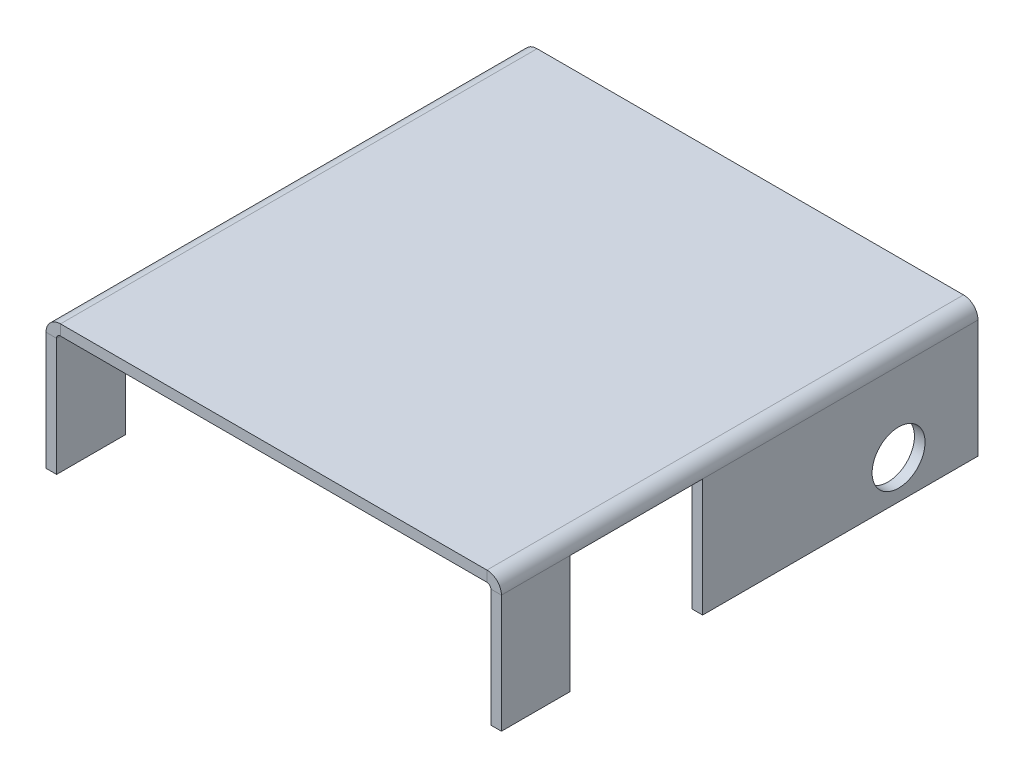
SolidWorks part; units mm, degrees
note: The reader was unsure of these and kept them because the rebuilt part matched: flange length of "Edge-Flange1", "Edge-Flange2".
ref_plane "Front Plane" through (0, 0, 0) normal (0, 0, 1) x (1, 0, 0)
ref_plane "Top Plane" through (0, 0, 0) normal (0, 1, 0) x (1, 0, 0)
ref_plane "Right Plane" through (0, 0, 0) normal (1, 0, 0) x (0, 0, -1)
sketch "Sketch1" plane through (0, 0, 0) normal (0, 1, 0) x (1, 0, 0)
  line L1 (4.0169, 90.0175) -> (90.0169, 90.0175)
  line L2 (4.0169, 90.0175) -> (4.0169, 0.0175)
  line L3 (4.0169, 0.0175) -> (90.0169, 0.0175)
  line L4 (90.0169, 90.0175) -> (90.0169, 0.0175)
  dimension "D1" = 86
  dimension "D2" = 90
base flange "Base-Flange1" sketch "Sketch1" thickness 2 reverse thickness direction no parameters "D1"=0.7366
edge flange "Edge-Flange1" sketch "Sketch8" flange angle 90 flange length 25 flange position material inside bend radius 0.7366 thickness 2 relief rectangular parameters "D6"=10
sketch "Sketch8" plane through (90.0169, -2, 0) normal (1, 0, 0) x (0, 0, 1)
  line L2 (-90.0175, 0) -> (-90.0175, 23)
  line L3 (-90.0175, 23) -> (-0.0175, 23)
  line L4 (-0.0175, 23) -> (-0.0175, 0)
  line L5 (-0.0175, 0) -> (-90.0175, 0) construction
  line L6 (-0.0175, 0) -> (-90.0175, 0)
bend "EdgeBend1" bend radius 0.7366 bend angle 90 parameters "D5"=1
edge flange "Edge-Flange2" sketch "Sketch11" flange angle 90 flange length 25 flange position material inside bend radius 0.7366 thickness 2 relief rectangular parameters "D6"=10
sketch "Sketch11" plane through (4.0169, -2, 0) normal (-1, 0, 0) x (0, 0, -1)
  line L0 (90.0175, 0) -> (0.0175, 0) construction
  line L1 (90.0175, 0) -> (0.0175, 0)
  line L2 (0.0175, 0) -> (0.0175, 23)
  line L3 (0.0175, 23) -> (90.0175, 23)
  line L4 (90.0175, 23) -> (90.0175, 0)
bend "EdgeBend2" bend radius 0.7366 bend angle 90 parameters "D5"=2
sketch "Sketch13" plane through (90.0169, 0, 0) normal (1, 0, 0) x (0, 0, -1)
  line L0 (0.0175, -25) -> (90.0175, -25) construction
  line L1 (38.0175, -25) -> (13.0175, -25)
  line L2 (38.0175, -25) -> (38.0175, -2.7366)
  line L3 (38.0175, -2.7366) -> (13.0175, -2.7366)
  line L4 (13.0175, -25) -> (13.0175, -2.7366)
  line L5 (0.0175, -2.7366) -> (90.0175, -2.7366) construction
  dimension "D1" = 25
  dimension "D2" = 13
extrude "Cut-Extrude1" cut sketch "Sketch13" against normal through all normal cut yes
sketch "Sketch15" plane through (4.0169, 0, 0) normal (-1, 0, 0) x (0, 0, 1)
  line L0 (-90.0175, -2.7366) -> (-38.0175, -2.7366) construction
  line L1 (-90.0175, -2.7366) -> (-90.0175, -25) construction
  circle A0 centre (-75.0175, -17.7366) radius 5
  dimension "D1" = 15
  dimension "D2" = 15
extrude "Cut-Extrude2" cut sketch "Sketch15" against normal through all normal cut yes
sketch "Bend-Lines1" [suppressed] plane through (0, 0, 0) normal (0, 1, 0) x (1, 0, 0)
sketch "Bounding-Box1" [suppressed] plane through (0, 0, 0) normal (0, 1, 0) x (1, 0, 0)
sheet metal parameters "Sheet-Metal1" thickness 2 parameters "D1"=0.7366
flat pattern "Flat-Pattern1" [suppressed]
sketch "Bend-Lines2" plane through (0, 0, 0) normal (0, 1, 0) x (1, 0, 0)
sketch3d "Bounding-Box2" [suppressed]
  line L0 (-90.0169, 0.0175, 0) -> (-0.0169, 0.0175, 0) construction
  line L1 (-90.0169, 90.0175, 0) -> (-0.0169, 90.0175, 0) construction
  line L2 (-90.0169, 0.0175, 0) -> (-90.0169, 90.0175, 0) construction
  line L3 (-0.0169, 0.0175, 0) -> (-0.0169, 90.0175, 0) construction
sheet metal parameters "Sheet-Metal2" thickness 2 parameters "D1"=0.7366
flat pattern "Flat-Pattern1"
sketch "Bend-Lines2" plane through (0, 0, 0) normal (0, 1, 0) x (1, 0, 0)
  line L0 (88.6442, 0.0175) -> (88.6442, 90.0175) construction
  line L1 (88.6442, 0.0175) -> (88.6442, 90.0175) construction
sketch3d "Bounding-Box2" [suppressed]
  line L0 (112.2715, 0.0175, 0) -> (0.0169, 0.0175, 0) construction
  line L1 (112.2715, 90.0175, 0) -> (0.0169, 90.0175, 0) construction
  line L2 (112.2715, 0.0175, 0) -> (112.2715, 90.0175, 0) construction
  line L3 (0.0169, 0.0175, 0) -> (0.0169, 90.0175, 0) construction
bend of the flat pattern "Flatten-<EdgeBend1>1"
sheet metal parameters "Sheet-Metal3" thickness 2 parameters "D1"=0.7366
flat pattern "Flat-Pattern1"
sketch "Bend-Lines2" plane through (0, 0, 0) normal (0, 1, 0) x (1, 0, 0)
  line L0 (88.6442, 0.0175) -> (88.6442, 90.0175) construction
  line L1 (88.6442, 0.0175) -> (88.6442, 90.0175) construction
  line L2 (1.3896, 90.0175) -> (1.3896, 0.0175) construction
  line L3 (1.3896, 90.0175) -> (1.3896, 0.0175) construction
sketch3d "Bounding-Box2" [suppressed]
  line L0 (112.2715, 0.0175, 0) -> (-22.2378, 0.0175, 0) construction
  line L1 (112.2715, 90.0175, 0) -> (-22.2378, 90.0175, 0) construction
  line L2 (112.2715, 0.0175, 0) -> (112.2715, 90.0175, 0) construction
  line L3 (-22.2378, 0.0175, 0) -> (-22.2378, 90.0175, 0) construction
bend of the flat pattern "Flatten-<EdgeBend1>1"
bend of the flat pattern "Flatten-<EdgeBend2>1"
sheet metal parameters "Sheet-Metal4" thickness 2 parameters "D1"=0.7366
flat pattern "Flat-Pattern1"
sketch "Bend-Lines2" plane through (0, 0, 0) normal (0, 1, 0) x (1, 0, 0)
  line L0 (88.6442, 0.0175) -> (88.6442, 90.0175) construction
  line L1 (88.6442, 0.0175) -> (88.6442, 90.0175) construction
  line L2 (1.3896, 90.0175) -> (1.3896, 0.0175) construction
  line L3 (1.3896, 90.0175) -> (1.3896, 0.0175) construction
sketch3d "Bounding-Box2" [suppressed]
  line L0 (112.2715, 0.0175, 0) -> (-22.2378, 0.0175, 0) construction
  line L1 (112.2715, 90.0175, 0) -> (-22.2378, 90.0175, 0) construction
  line L2 (112.2715, 0.0175, 0) -> (112.2715, 90.0175, 0) construction
  line L3 (-22.2378, 0.0175, 0) -> (-22.2378, 90.0175, 0) construction
bend of the flat pattern "Flatten-<EdgeBend1>1"
bend of the flat pattern "Flatten-<EdgeBend2>1"
sheet metal parameters "Sheet-Metal5" thickness 2 parameters "D1"=0.7366
flat pattern "Flat-Pattern1"
sketch "Bend-Lines2" plane through (0, 0, 0) normal (0, 1, 0) x (1, 0, 0)
  line L0 (88.6442, 0.0175) -> (88.6442, 90.0175) construction
  line L1 (88.6442, 0.0175) -> (88.6442, 90.0175) construction
  line L2 (1.3896, 90.0175) -> (1.3896, 0.0175) construction
  line L3 (1.3896, 90.0175) -> (1.3896, 0.0175) construction
sketch3d "Bounding-Box2" [suppressed]
  line L0 (112.2715, 0.0175, 0) -> (-22.2378, 0.0175, 0) construction
  line L1 (112.2715, 90.0175, 0) -> (-22.2378, 90.0175, 0) construction
  line L2 (112.2715, 0.0175, 0) -> (112.2715, 90.0175, 0) construction
  line L3 (-22.2378, 0.0175, 0) -> (-22.2378, 90.0175, 0) construction
bend of the flat pattern "Flatten-<EdgeBend1>1"
bend of the flat pattern "Flatten-<EdgeBend2>1"
